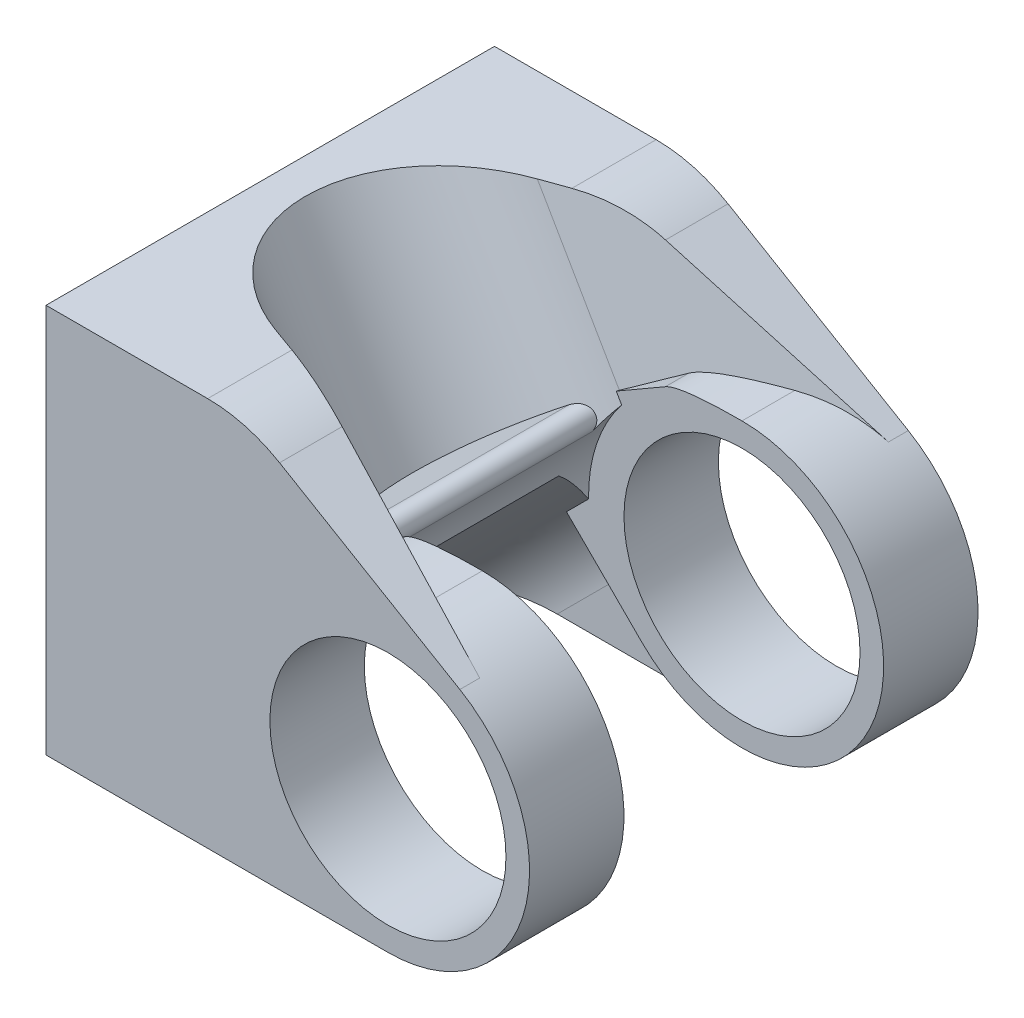
SolidWorks part; units mm, degrees
ref_plane "Спереди" through (0, 0, 0) normal (0, 0, 1) x (1, 0, 0)
ref_plane "Сверху" through (0, 0, 0) normal (0, 1, 0) x (1, 0, 0)
ref_plane "Справа" through (0, 0, 0) normal (1, 0, 0) x (0, 0, -1)
sketch "Эскиз1" plane through (0, 0, 0) normal (0, 0, 1) x (1, 0, 0)
  line L0 (-8.4456, 2.6295) -> (-12.9897, 10.5) construction
  line L1 (-4.2426, 4.2426) -> (-14.4853, -6) construction
  line L2 (-14.4853, -6) -> (0, -6)
  line L3 (0, 0) -> (0, 6) construction
  line L9 (-3.25, 5.6292) -> (-8.4456, 2.6295) construction
  line L11 (0, 6) -> (0, 6.5) construction
  line L14 (-6, 10.5) -> (3.0462, 5.1692)
  line L15 (-14.4853, -6) -> (-14.4853, 10.5)
  line L16 (-14.4853, 10.5) -> (-6, 10.5)
  line L23 (-4.2426, -4.2426) -> (-4.5962, -4.5962) construction
  circle A0 centre (0, 0) radius 5
  circle A1 centre (0, 0) radius 6
  circle A4 centre (0, 0) radius 6.5 construction
  arc A5 (-5.7513, 3.0287) -> (-6.3123, 1.5509) centre (0, 0) ccw
  arc A14 (-6.5025, 3.7513) -> (-5.7513, 3.0287) centre (-6.2313, 3.2815) cw
  arc A16 (-6.3123, 1.5509) -> (-8.9809, -0.4956) centre (0.1088, -9.5852) ccw
sketch "Эскиз2" plane through (0, 0, 0) normal (0, 0, 1) x (1, 0, 0)
  line L0 (3.0462, 5.1692) -> (-6, 10.5)
  line L1 (-6, 10.5) -> (-14.4853, 10.5)
  line L2 (-14.4853, 10.5) -> (-14.4853, -6)
  line L3 (-14.4853, -6) -> (0, -6)
  arc A0 (0, -6) -> (3.0462, 5.1692) centre (0, 0) ccw
extrude "Бобышка-Вытянуть1" add sketch "Эскиз2" along normal mid plane 19
ref_plane "Плоскость1" through (-3.25, 5.6292, 0) normal (-0.5, 0.866, 0) x (0.866, 0.5, 0)
sketch "Эскиз3" plane through (-3.25, 5.6292, 0) normal (-0.5, 0.866, 0) x (0.866, 0.5, 0)
  line L1 (-2.2961, -5.5433) -> (6, -8.9796)
  line L4 (0, 0) -> (-4.2426, 4.2426) construction
  line L5 (-4.2426, 4.2426) -> (0, 6) construction
  line L6 (-2.1213, 5.1213) -> (-2.2961, 5.5433) construction
  line L7 (-2.2961, 5.5433) -> (6, 8.9796)
  line L8 (6, -9.5) -> (6, 9.5) construction
  line L9 (6, 8.9796) -> (6, -8.9796)
  line L10 (6, 0) -> (0, 0) construction
  circle A0 centre (0, 0) radius 6
extrude "Вырез-Вытянуть1" cut sketch "Эскиз3" along normal through all both and the other way through all contours A0 | A0 L1 L9 | A0 L9 L7 region at (0.2308, 7.6388, 6.0152) region at (-3.25, 5.6292, 0) region at (0.2308, 7.6388, -6.0152)
ref_plane "Плоскость2" through (-4.2426, 4.2426, 0) normal (-0.7071, -0.7071, 0) x (-0.7071, 0.7071, 0)
sketch "Эскиз4" plane through (-4.2426, 4.2426, 0) normal (-0.7071, -0.7071, 0) x (-0.7071, 0.7071, 0)
  line L1 (0, -6.5) -> (-12, -6.5)
  line L2 (0, -6.5) -> (0, 6.5)
  line L3 (0, 6.5) -> (-12, 6.5)
  line L4 (-12, -6.5) -> (-12, 6.5)
  line L5 (0, -6.5) -> (-12, 6.5) construction
  line L6 (0, 6.5) -> (-12, -6.5) construction
  line L8 (0, -6.5) -> (0, -2) construction
  line L9 (0, -2) -> (-4, -2) construction
  line L10 (-6, 0) -> (0, 0) construction
  ellipse E0 centre (-4, -2) end of major axis (-4, -6.5) minor radius 4 (0, -2) -> (-4, -6.5) cw
  ellipse E1 centre (-4, 2) end of major axis (-4, 6.5) minor radius 4 (0, 2) -> (-4, 6.5) ccw
  point P0 (-6, 0)
extrude "Вырез-Вытянуть3" cut sketch "Эскиз4" against normal through all both and the other way through all contours L2 E1 L3 L4 L1 E0 region at (0.1881, -0.1881, 0)
sketch "Эскиз5" plane through (0, 0, 0) normal (0, 0, 1) x (1, 0, 0)
  circle A0 centre (0, 0) radius 6.5
extrude "Вырез-Вытянуть4" cut sketch "Эскиз5" against normal mid plane 13
sketch "Эскиз6" plane through (0, 0, 0) normal (0, 0, 1) x (1, 0, 0)
  line L0 (-6.5025, 3.7513) -> (-8.4456, 2.6295)
  line L1 (-8.4456, 2.6295) -> (-8.9809, -0.4956)
  arc A0 (-8.9809, -0.4956) -> (-6.3123, 1.5509) centre (0.1088, -9.5852) cw
  arc A1 (-5.7513, 3.0287) -> (-6.3123, 1.5509) centre (0, 0) ccw construction
  arc A2 (-6.3123, 1.5509) -> (-5.7513, 3.0287) centre (0, 0) cw
  arc A3 (-5.7513, 3.0287) -> (-6.5025, 3.7513) centre (-6.2313, 3.2815) ccw
  arc A4 (-5.7513, 3.0287) -> (-6.5025, 3.7513) centre (-6.2313, 3.2815) ccw construction
extrude "Бобышка-Вытянуть2" add sketch "Эскиз6" along normal mid plane 13
sketch "Эскиз9" plane through (0, 0, 6.5) normal (0, 0, -1) x (-1, 0, 0)
  line L0 (0, 0) -> (0, 6) construction
  line L1 (0, 0) -> (1.5, 2.5981) construction
  line L2 (1.5, 2.5981) -> (3, 5.1962) construction
  line L3 (3, 5.1962) -> (3.25, 5.6292) construction
  line L5 (3.25, 5.6292) -> (10.1378, 1.6525)
  line L6 (4.2426, -4.2426) -> (10.1378, 1.6525)
  line L7 (0, 0) -> (4.2426, -4.2426) construction
  line L8 (0, 6) -> (2.6077, 6) construction
  line L9 (3.25, 5.6292) -> (2.6077, 6) construction
  line L10 (3.25, 5.6292) -> (2.6077, 6) construction
  line L11 (2.6077, 6) -> (0, 6) construction
  circle A0 centre (0, 0) radius 6
  arc A1 (0, 3) -> (1.5, 2.5981) centre (0, 0) cw
  spline S0 degree 2 poles (3.25, 5.6292) (2.6077, 6) (0, 6) knots 0 0 0 1 1 1
  arc M4 (5.7874, -2.959) -> (3.2382, 5.636) centre (0, 0) ccw
  line M12 (3.2382, 5.636) -> (-3.0118, -5.1893)
  arc M13 (-3.0118, -5.1893) -> (0, -6) centre (0, 0) ccw
extrude "Бобышка-Вытянуть3" add sketch "Эскиз9" against normal blind 3 and the other way blind 1 contours A0 M12 | A0 M13 M12 | L6 L5 M4 | S0 A0 M12 | S0 A0 L6 M4 M12 region at (-6.0536, 2.062, 6.5) region at (-7.3524, 1.4681, 6.5) region at (-2.313, 5.6873, 6.5) region at (2.2117, 1.2769, 6.5) region at (-2.1989, -1.2696, 6.5)
mirror "Зеркальное отражение1" about plane through (0, 0, 0) normal (0, 0, 1) of "Бобышка-Вытянуть3"
sketch "Эскиз10" plane through (0, 0, 0) normal (0, 0, 1) x (1, 0, 0)
  circle A0 centre (0, 0) radius 5
extrude "Вырез-Вытянуть5" cut sketch "Эскиз10" against normal through all both and the other way through all
fillet "Скругление1" radius 6 2 edges at (-6, 10.5, 8.0083) (-6, 10.5, -8.0083)
